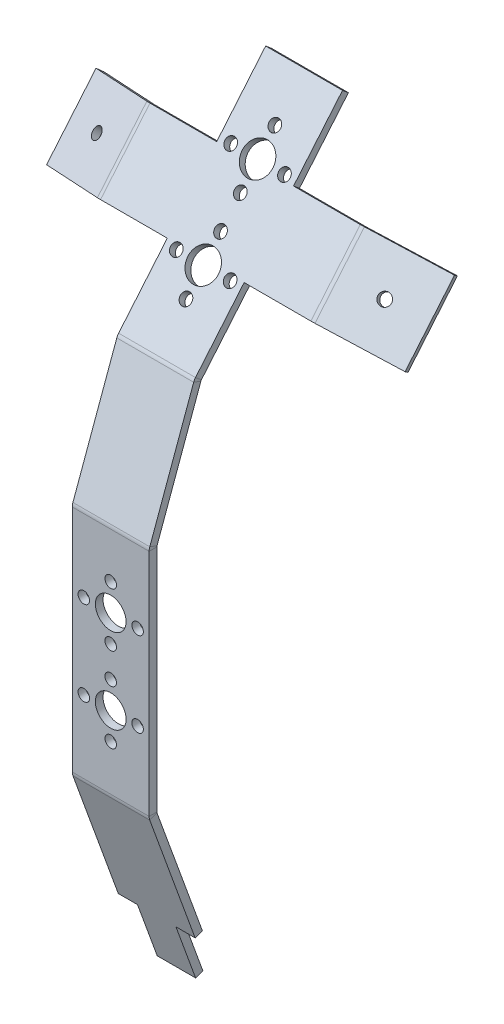
SolidWorks part; units mm, degrees
note: The reader was unsure of these and kept them because the rebuilt part matched: flange length of "Edge-Flange1", "Edge-Flange2", "Edge-Flange3", "Edge-Flange4".
ref_plane "Front Plane" through (0, 0, 0) normal (0, 0, 1) x (1, 0, 0)
ref_plane "Top Plane" through (0, 0, 0) normal (0, 1, 0) x (1, 0, 0)
ref_plane "Right Plane" through (0, 0, 0) normal (1, 0, 0) x (0, 0, -1)
sketch "Sketch1" plane through (0, 0, 0) normal (0, 0, 1) x (1, 0, 0)
  line L1 (-10, -30) -> (10, -30)
  line L2 (-10, -30) -> (-10, 30)
  line L3 (-10, 30) -> (10, 30)
  line L4 (10, -30) -> (10, 30)
  line L5 (-10, -30) -> (10, 30) construction
  line L6 (-10, 30) -> (10, -30) construction
  point P0 (0, 0)
  dimension "D1" = 20
  dimension "D2" = 60
base flange "Base-Flange1" sketch "Sketch1" thickness 2 reverse thickness direction no parameters "D1"=0.7366
sketch "Sketch2" plane through (0, 0, 0) normal (0, 0, 1) x (1, 0, 0)
  line L0 (0, 30) -> (0, -30) construction
  line L1 (10, 30) -> (-10, 30) construction
  line L2 (-10, -30) -> (10, -30) construction
  line L3 (-10, 0) -> (10, 0) construction
  line L4 (-10, 30) -> (-10, -30) construction
  line L5 (10, -30) -> (10, 30) construction
  circle A0 centre (0, 11) radius 4
  circle A2 centre (0, 18) radius 1.5
  circle A3 centre (7, 11) radius 1.5
  circle A4 centre (0, 4) radius 1.5
  circle A5 centre (-7, 11) radius 1.5
  circle A6 centre (0, -18) radius 1.5
  circle A7 centre (7, -11) radius 1.5
  circle A8 centre (0, -4) radius 1.5
  circle A9 centre (0, -11) radius 4
  circle A10 centre (-7, -11) radius 1.5
  point P20 (0, 11)
  dimension "D1" = 8
  dimension "D3" = 7
  dimension "D4" = 3
  dimension "D2" = 11
  dimension "D5" = 4
extrude "Cut-Extrude1" cut sketch "Sketch2" against normal blind 2 contours A0 | A2 | A3 | A4 | A5 | A9 | A8 | A7 | A10 | A6 normal cut yes
edge flange "Edge-Flange1" sketch "Sketch9" flange angle 160 flange length 34 flange position material outside bend radius 0.7366 thickness 2 relief rectangular parameters "D6"=10
sketch "Sketch9" plane through (0, 30, -2) normal (0, 0.342, 0.9397) x (1, 0, 0)
  line L0 (10, 0) -> (-10, 0) construction
  line L1 (10, 0) -> (-10, 0)
  line L2 (-10, 0) -> (-10, 33.6473)
  line L3 (-10, 33.6473) -> (10, 33.6473)
  line L4 (10, 33.6473) -> (10, 0)
bend "EdgeBend1" bend radius 0.7366 bend angle 20 parameters "D5"=1
edge flange "Edge-Flange2" sketch "Sketch12" flange angle 160 flange length 50 flange position material outside bend radius 0.7366 thickness 2 relief rectangular parameters "D6"=10
sketch "Sketch12" plane through (0, -30, -2) normal (0, -0.342, 0.9397) x (-1, 0, 0)
  line L0 (10, 0) -> (-10, 0) construction
  line L1 (10, 0) -> (-10, 0)
  line L2 (-10, 0) -> (-10, 49.6473)
  line L3 (-10, 49.6473) -> (10, 49.6473)
  line L4 (10, 49.6473) -> (10, 0)
bend "EdgeBend2" bend radius 0.7366 bend angle 20 parameters "D5"=2
edge flange "Edge-Flange3" sketch "Sketch15" flange angle 160 flange length 60 flange position material outside bend radius 0.7366 thickness 2 relief rectangular parameters "D6"=10
sketch "Sketch15" plane through (0, 61.6182, -13.5081) normal (0, 0.6428, 0.766) x (1, 0, 0)
  line L0 (10, 0) -> (-10, 0) construction
  line L1 (10, 0) -> (-10, 0)
  line L2 (-10, 0) -> (-10, 19.8237)
  line L3 (-10, 59.6473) -> (10, 59.6473)
  line L4 (10, 59.6473) -> (10, 39.8237)
  line L5 (7.586, 29.8237) -> (-46.5431, 29.8237) construction
  line L6 (10, 19.8237) -> (10, 0)
  line L7 (27.5, 19.8237) -> (10, 19.8237)
  line L8 (27.5, 19.8237) -> (27.5, 39.8237)
  line L9 (27.5, 39.8237) -> (10, 39.8237)
  line L11 (27.5, 19.8237) -> (10, 39.8237) construction
  line L12 (27.5, 39.8237) -> (10, 19.8237) construction
  line L13 (-27.5, 19.8237) -> (-10, 19.8237)
  line L14 (-27.5, 19.8237) -> (-27.5, 39.8237)
  line L15 (-27.5, 39.8237) -> (-10, 39.8237)
  line L17 (-27.5, 19.8237) -> (-10, 39.8237) construction
  line L18 (-27.5, 39.8237) -> (-10, 19.8237) construction
  line L19 (-10, 39.8237) -> (-10, 59.6473)
  point P6 (18.75, 29.8237)
  point P12 (-18.75, 29.8237)
  dimension "D1" = 20
  dimension "D2" = 17.5
bend "EdgeBend3" bend radius 0.7366 bend angle 20 parameters "D5"=3
sketch "Sketch16" plane through (0, -3.5506, 9.7552) normal (0, -0.342, 0.9397) x (1, 0, 0)
  line L1 (-10, -78.5222) -> (-5, -78.5222)
  line L2 (-10, -78.5222) -> (-10, -63.5222)
  line L3 (-10, -63.5222) -> (-5, -63.5222)
  line L4 (-5, -78.5222) -> (-5, -63.5222)
  line L5 (10, -78.5222) -> (5, -78.5222)
  line L6 (10, -78.5222) -> (10, -63.5222)
  line L7 (10, -63.5222) -> (5, -63.5222)
  line L8 (5, -78.5222) -> (5, -63.5222)
  dimension "D1" = 10
  dimension "D2" = 15
edge flange "Edge-Flange4" sketch "Sketch21" flange profiles "Sketch21", "Sketch22" flange angle 160 flange length 20 flange position material outside bend radius 0.7366 thickness 2 relief rectangular parameters "D6"=10, "D8"=1
sketch "Sketch21" plane through (27.5, 18.8077, 22.4142) normal (0.342, 0.604, 0.7198) x (0, -0.766, 0.6428)
  line L0 (-75.7087, 0) -> (-95.7087, 0) construction
  line L1 (-75.7087, 0) -> (-95.7087, 0)
  line L2 (-95.7087, 0) -> (-95.7087, 19.6473)
  line L3 (-95.7087, 19.6473) -> (-75.7087, 19.6473)
  line L4 (-75.7087, 19.6473) -> (-75.7087, 0)
sketch "Sketch22" plane through (-27.5, 18.8077, 22.4142) normal (-0.342, 0.604, 0.7198) x (0, 0.766, -0.6428)
  line L0 (95.7087, 0) -> (75.7087, 0) construction
  line L1 (95.7087, 0) -> (75.7087, 0)
  line L2 (75.7087, 0) -> (75.7087, 19.6473)
  line L3 (75.7087, 19.6473) -> (95.7087, 19.6473)
  line L4 (95.7087, 19.6473) -> (95.7087, 0)
bend "EdgeBend4" bend radius 0.7366 bend angle 20 parameters "D5"=4
bend "EdgeBend5" bend radius 0.7366 bend angle 20 parameters "D5"=5
extrude "Cut-Extrude2" cut sketch "Sketch16" against normal through all normal cut yes
sketch "Sketch23" plane through (0, 20.0933, 23.9463) normal (0, 0.6428, 0.766) x (1, 0, 0)
  line L0 (0, 115.5324) -> (0, 56.015) construction
  line L1 (-10, 115.5324) -> (10, 115.5324) construction
  line L2 (-27.3701, 85.7087) -> (27.3701, 85.7087) construction
  line L3 (-27.3701, 95.7087) -> (-27.3701, 75.7087) construction
  line L4 (27.3701, 75.7087) -> (27.3701, 95.7087) construction
  line L5 (10, 56.015) -> (-10, 56.015) construction
  circle A0 centre (0, 96.7087) radius 4
  circle A1 centre (0, 103.7087) radius 1.5
  circle A2 centre (7, 96.7087) radius 1.5
  circle A3 centre (0, 89.7087) radius 1.5
  circle A4 centre (-7, 96.7087) radius 1.5
  circle A5 centre (0, 74.7087) radius 4
  circle A6 centre (7, 74.7087) radius 1.5
  circle A7 centre (0, 81.7087) radius 1.5
  circle A8 centre (-7, 74.7087) radius 1.5
  circle A9 centre (0, 67.7087) radius 1.5
  point P25 (0, 96.7087)
  dimension "D1" = 11
  dimension "D2" = 7
  dimension "D3" = 8
  dimension "D4" = 3
  dimension "D6" = 7
  dimension "D5" = 4
extrude "Cut-Extrude3" cut sketch "Sketch23" against normal blind 10 normal cut yes
sketch "Sketch24" plane through (-12.6207, 22.2888, 26.5628) normal (0.342, -0.604, -0.7198) x (-0.9397, -0.2198, -0.262)
  line L0 (25.6578, 95.7087) -> (25.7228, 75.7087) construction
  line L1 (35.4815, 95.7087) -> (15.8342, 95.7087) construction
  line L2 (35.4815, 75.7087) -> (15.9641, 75.7087) construction
  circle A0 centre (25.6903, 85.7087) radius 1.5
  dimension "D1" = 3
extrude "Cut-Extrude4" cut sketch "Sketch24" against normal blind 10 normal cut yes
sketch "Sketch25" plane through (12.6207, 22.2888, 26.5628) normal (-0.342, -0.604, -0.7198) x (-0.9397, 0.2198, 0.262)
  line L0 (-25.7228, 95.7087) -> (-25.7228, 75.7087) construction
  line L3 (-35.4815, 95.7087) -> (-15.9641, 95.7087) construction
  line L4 (-15.9641, 75.7087) -> (-35.4815, 75.7087) construction
  circle A0 centre (-25.7228, 85.7087) radius 1.5
  dimension "D1" = 3
extrude "Cut-Extrude5" cut sketch "Sketch25" against normal blind 10 normal cut yes
sketch "Bend-Lines1" [suppressed] plane through (0, 0, 0) normal (0, 1, 0) x (1, 0, 0)
sketch "Bounding-Box1" [suppressed] plane through (0, 0, 0) normal (0, 1, 0) x (1, 0, 0)
sheet metal parameters "Sheet-Metal2" thickness 2 parameters "D1"=0.7366
flat pattern "Flat-Pattern2" [suppressed]
sketch "Bend-Lines2" plane through (0, 0, 0) normal (0, 1, 0) x (1, 0, 0)
sketch3d "Bounding-Box2" [suppressed]
  line L0 (10, 30, 0) -> (10, -30, 0) construction
  line L1 (-10, 30, 0) -> (-10, -30, 0) construction
  line L2 (10, 30, 0) -> (-10, 30, 0) construction
  line L3 (10, -30, 0) -> (-10, -30, 0) construction
sheet metal parameters "Sheet-Metal3" thickness 2 parameters "D1"=0.7366
flat pattern "Flat-Pattern2"
sketch "Bend-Lines2" plane through (0, 0, 0) normal (0, 1, 0) x (1, 0, 0)
sketch3d "Bounding-Box2" [suppressed]
  line L0 (10, 30, 0) -> (10, -30, 0) construction
  line L1 (-10, 30, 0) -> (-10, -30, 0) construction
  line L2 (10, 30, 0) -> (-10, 30, 0) construction
  line L3 (10, -30, 0) -> (-10, -30, 0) construction
sheet metal parameters "Sheet-Metal4" thickness 2 parameters "D1"=0.7366
flat pattern "Flat-Pattern2"
sketch "Bend-Lines2" plane through (0, 0, 0) normal (0, 0, 1) x (1, 0, 0)
  line L0 (10, 30.2156) -> (-10, 30.2156) construction
  line L1 (10, 30.2156) -> (-10, 30.2156) construction
sketch3d "Bounding-Box2" [suppressed]
  line L0 (10, 74.9877, 0) -> (10, -30, 0) construction
  line L1 (-10, 74.9877, 0) -> (-10, -30, 0) construction
  line L2 (10, 74.9877, 0) -> (-10, 74.9877, 0) construction
  line L3 (10, -30, 0) -> (-10, -30, 0) construction
bend of the flat pattern "Flatten-<EdgeBend1>1"
sheet metal parameters "Sheet-Metal5" thickness 2 parameters "D1"=0.7366
flat pattern "Flat-Pattern2"
sketch "Bend-Lines2" plane through (0, 0, 0) normal (0, 0, 1) x (1, 0, 0)
  line L0 (10, 30.2323) -> (-10, 30.2323) construction
  line L1 (10, 30.2323) -> (-10, 30.2323) construction
  line L2 (-10, -30.1732) -> (10, -30.1732) construction
  line L3 (-10, -30.1732) -> (10, -30.1732) construction
sketch3d "Bounding-Box2" [suppressed]
  line L0 (10, 69.9845, 0) -> (10, -84.9938, 0) construction
  line L1 (-10, 69.9845, 0) -> (-10, -84.9938, 0) construction
  line L2 (10, 69.9845, 0) -> (-10, 69.9845, 0) construction
  line L3 (10, -84.9938, 0) -> (-10, -84.9938, 0) construction
bend of the flat pattern "Flatten-<EdgeBend1>1"
bend of the flat pattern "Flatten-<EdgeBend2>1"
sheet metal parameters "Sheet-Metal6" thickness 2 parameters "D1"=0.7366
flat pattern "Flat-Pattern2"
sketch "Bend-Lines2" plane through (0, 0, 0) normal (0, 0, 1) x (1, 0, 0)
  line L0 (10, 30.1732) -> (-10, 30.1732) construction
  line L1 (10, 30.1732) -> (-10, 30.1732) construction
  line L2 (-10, -30.1732) -> (10, -30.1732) construction
  line L3 (-10, -30.1732) -> (10, -30.1732) construction
  line L4 (10, 70.167) -> (-10, 70.167) construction
  line L5 (10, 70.167) -> (-10, 70.167) construction
sketch3d "Bounding-Box2" [suppressed]
  line L0 (20, 119.9742, 0) -> (20, -79.9938, 0) construction
  line L1 (-20, 119.9742, 0) -> (-20, -79.9938, 0) construction
  line L2 (20, 119.9742, 0) -> (-20, 119.9742, 0) construction
  line L3 (20, -79.9938, 0) -> (-20, -79.9938, 0) construction
bend of the flat pattern "Flatten-<EdgeBend1>1"
bend of the flat pattern "Flatten-<EdgeBend2>1"
bend of the flat pattern "Flatten-<EdgeBend3>1"
sheet metal parameters "Sheet-Metal7" thickness 2 parameters "D1"=0.7366
flat pattern "Flat-Pattern2"
sketch "Bend-Lines2" plane through (0, 0, 0) normal (0, 0, 1) x (1, 0, 0)
  line L0 (10, 30.1518) -> (-10, 30.1518) construction
  line L1 (10, 30.1518) -> (-10, 30.1518) construction
  line L2 (-10, -30.1732) -> (10, -30.1732) construction
  line L3 (-10, -30.1732) -> (10, -30.1732) construction
  line L4 (10, 65.1903) -> (-10, 65.1903) construction
  line L5 (10, 65.1903) -> (-10, 65.1903) construction
  line L6 (-27.6732, 105.1858) -> (-27.6732, 85.1858) construction
  line L7 (27.6732, 85.1858) -> (27.6732, 105.1858) construction
  line L8 (-27.6732, 105.1858) -> (-27.6732, 85.1858) construction
  line L9 (27.6732, 85.1858) -> (27.6732, 105.1858) construction
sketch3d "Bounding-Box2" [suppressed]
  line L0 (47.4938, 124.9869, 0) -> (47.4938, -79.9938, 0) construction
  line L1 (-47.4938, 124.9869, 0) -> (-47.4938, -79.9938, 0) construction
  line L2 (47.4938, 124.9869, 0) -> (-47.4938, 124.9869, 0) construction
  line L3 (47.4938, -79.9938, 0) -> (-47.4938, -79.9938, 0) construction
bend of the flat pattern "Flatten-<EdgeBend1>1"
bend of the flat pattern "Flatten-<EdgeBend2>1"
bend of the flat pattern "Flatten-<EdgeBend3>1"
bend of the flat pattern "Flatten-<EdgeBend5>2"
bend of the flat pattern "Flatten-<EdgeBend4>2"
sheet metal parameters "Sheet-Metal8" thickness 2 parameters "D1"=0.7366
flat pattern "Flat-Pattern2"
sketch "Bend-Lines2" plane through (0, 0, 0) normal (0, 0, 1) x (1, 0, 0)
  line L0 (10, 30.1732) -> (-10, 30.1732) construction
  line L1 (10, 30.1732) -> (-10, 30.1732) construction
  line L2 (-10, -30.1732) -> (10, -30.1732) construction
  line L3 (-10, -30.1732) -> (10, -30.1732) construction
  line L4 (10, 70.167) -> (-10, 70.167) construction
  line L5 (10, 70.167) -> (-10, 70.167) construction
  line L6 (-20.0871, 105.1572) -> (-20.0871, 85.1572) construction
  line L7 (20.0871, 85.1572) -> (20.0871, 105.1572) construction
  line L8 (-20.0871, 105.1572) -> (-20.0871, 85.1572) construction
  line L9 (20.0871, 85.1572) -> (20.0871, 105.1572) construction
sketch3d "Bounding-Box2" [suppressed]
  line L0 (39.9992, 119.9742, 0) -> (39.9992, -79.9938, 0) construction
  line L1 (-39.9992, 119.9742, 0) -> (-39.9992, -79.9938, 0) construction
  line L2 (39.9992, 119.9742, 0) -> (-39.9992, 119.9742, 0) construction
  line L3 (39.9992, -79.9938, 0) -> (-39.9992, -79.9938, 0) construction
bend of the flat pattern "Flatten-<EdgeBend1>1"
bend of the flat pattern "Flatten-<EdgeBend2>1"
bend of the flat pattern "Flatten-<EdgeBend3>1"
bend of the flat pattern "Flatten-<EdgeBend4>1"
bend of the flat pattern "Flatten-<EdgeBend5>1"
sheet metal parameters "Sheet-Metal9" thickness 2 parameters "D1"=0.7366
flat pattern "Flat-Pattern2"
sketch "Bend-Lines2" plane through (0, 0, 0) normal (0, 0, 1) x (1, 0, 0)
  line L0 (10, 30.1732) -> (-10, 30.1732) construction
  line L1 (10, 30.1732) -> (-10, 30.1732) construction
  line L2 (-10, -30.1732) -> (10, -30.1732) construction
  line L3 (-10, -30.1732) -> (10, -30.1732) construction
  line L4 (10, 64.167) -> (-10, 64.167) construction
  line L5 (10, 64.167) -> (-10, 64.167) construction
  line L6 (-27.6732, 104.1639) -> (-27.6732, 84.1639) construction
  line L7 (27.6732, 84.1639) -> (27.6732, 104.1639) construction
  line L8 (-27.6732, 104.1639) -> (-27.6732, 84.1639) construction
  line L9 (27.6732, 84.1639) -> (27.6732, 104.1639) construction
sketch3d "Bounding-Box2" [suppressed]
  line L0 (47.4938, 123.9875, 0) -> (47.4938, -79.9938, 0) construction
  line L1 (-47.4938, 123.9875, 0) -> (-47.4938, -79.9938, 0) construction
  line L2 (47.4938, 123.9875, 0) -> (-47.4938, 123.9875, 0) construction
  line L3 (47.4938, -79.9938, 0) -> (-47.4938, -79.9938, 0) construction
bend of the flat pattern "Flatten-<EdgeBend1>1"
bend of the flat pattern "Flatten-<EdgeBend2>1"
bend of the flat pattern "Flatten-<EdgeBend3>1"
bend of the flat pattern "Flatten-<EdgeBend5>2"
bend of the flat pattern "Flatten-<EdgeBend4>2"
sheet metal parameters "Sheet-Metal10" thickness 2 parameters "D1"=0.7366
flat pattern "Flat-Pattern2"
sketch "Bend-Lines2" plane through (0, 0, 0) normal (0, 0, 1) x (1, 0, 0)
  line L0 (10, 30.1732) -> (-10, 30.1732) construction
  line L1 (10, 30.1732) -> (-10, 30.1732) construction
  line L2 (-10, -30.1732) -> (10, -30.1732) construction
  line L3 (-10, -30.1732) -> (10, -30.1732) construction
  line L4 (10, 64.167) -> (-10, 64.167) construction
  line L5 (10, 64.167) -> (-10, 64.167) construction
  line L6 (-27.6732, 104.1639) -> (-27.6732, 84.1639) construction
  line L7 (27.6732, 84.1639) -> (27.6732, 104.1639) construction
  line L8 (-27.6732, 104.1639) -> (-27.6732, 84.1639) construction
  line L9 (27.6732, 84.1639) -> (27.6732, 104.1639) construction
sketch3d "Bounding-Box2" [suppressed]
  line L0 (47.4938, 123.9875, 0) -> (47.4938, -79.9938, 0) construction
  line L1 (-47.4938, 123.9875, 0) -> (-47.4938, -79.9938, 0) construction
  line L2 (47.4938, 123.9875, 0) -> (-47.4938, 123.9875, 0) construction
  line L3 (47.4938, -79.9938, 0) -> (-47.4938, -79.9938, 0) construction
bend of the flat pattern "Flatten-<EdgeBend1>1"
bend of the flat pattern "Flatten-<EdgeBend2>1"
bend of the flat pattern "Flatten-<EdgeBend3>1"
bend of the flat pattern "Flatten-<EdgeBend5>2"
bend of the flat pattern "Flatten-<EdgeBend4>2"
sheet metal parameters "Sheet-Metal11" thickness 2 parameters "D1"=0.7366
flat pattern "Flat-Pattern2"
sketch "Bend-Lines2" plane through (0, 0, 0) normal (0, 0, 1) x (1, 0, 0)
  line L0 (10, 30.1732) -> (-10, 30.1732) construction
  line L1 (10, 30.1732) -> (-10, 30.1732) construction
  line L2 (-10, -30.1732) -> (10, -30.1732) construction
  line L3 (-10, -30.1732) -> (10, -30.1732) construction
  line L4 (10, 64.167) -> (-10, 64.167) construction
  line L5 (10, 64.167) -> (-10, 64.167) construction
  line L6 (-27.6732, 104.1639) -> (-27.6732, 84.1639) construction
  line L7 (27.6732, 84.1639) -> (27.6732, 104.1639) construction
  line L8 (-27.6732, 104.1639) -> (-27.6732, 84.1639) construction
  line L9 (27.6732, 84.1639) -> (27.6732, 104.1639) construction
sketch3d "Bounding-Box2" [suppressed]
  line L0 (47.4938, 123.9875, 0) -> (47.4938, -79.9938, 0) construction
  line L1 (-47.4938, 123.9875, 0) -> (-47.4938, -79.9938, 0) construction
  line L2 (47.4938, 123.9875, 0) -> (-47.4938, 123.9875, 0) construction
  line L3 (47.4938, -79.9938, 0) -> (-47.4938, -79.9938, 0) construction
bend of the flat pattern "Flatten-<EdgeBend1>1"
bend of the flat pattern "Flatten-<EdgeBend2>1"
bend of the flat pattern "Flatten-<EdgeBend3>1"
bend of the flat pattern "Flatten-<EdgeBend5>2"
bend of the flat pattern "Flatten-<EdgeBend4>2"
